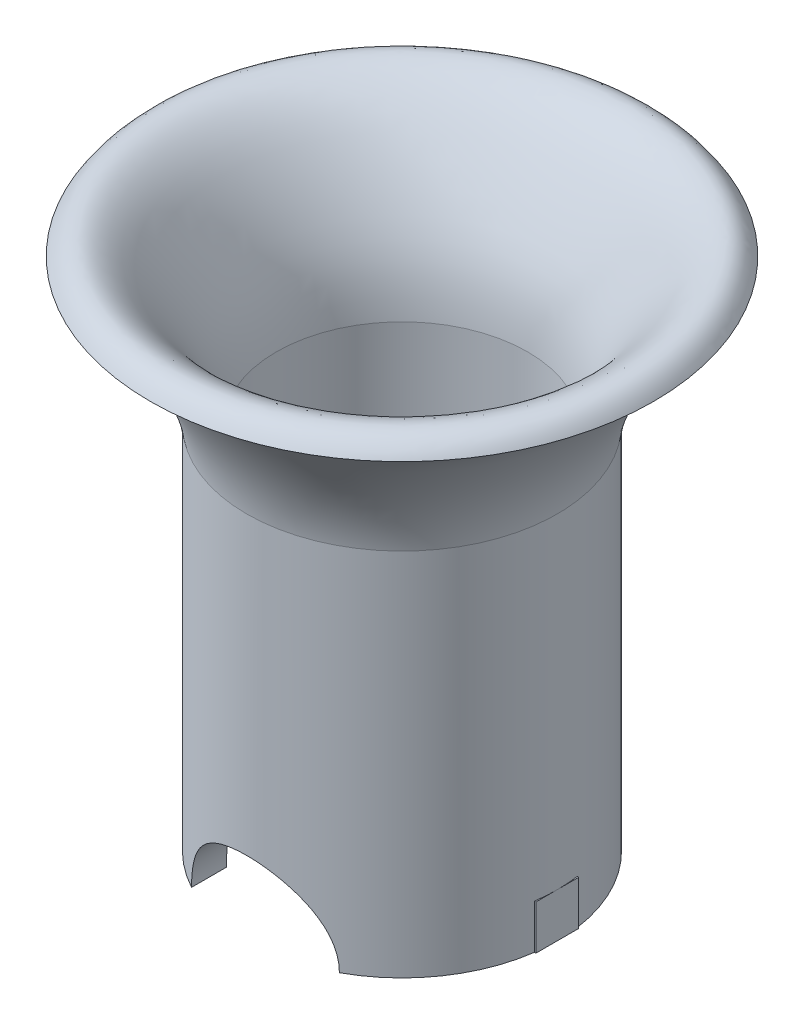
SolidWorks part; units mm, degrees
ref_plane "Front Plane" through (0, 0, 0) normal (0, 0, 1) x (1, 0, 0)
ref_plane "Top Plane" through (0, 0, 0) normal (0, 1, 0) x (1, 0, 0)
ref_plane "Right Plane" through (0, 0, 0) normal (1, 0, 0) x (0, 0, -1)
sketch "Sketch1" plane through (0, 0, 0) normal (0, 0, 1) x (1, 0, 0)
  line L0 (0, 0) -> (-8.5, 0) construction
  line L1 (-8.5, 0) -> (-8.5, 25)
  line L2 (-8.5, 0) -> (-10.5, 0)
  line L3 (-10.5, 0) -> (-10.5, 25)
  line L5 (0, 0) -> (0, 26.9305) construction
  spline S0 degree 3 poles (-8.5, 25) (-8.597, 26.015) (-8.907, 27.9673) (-10.2035, 30.7165) (-11.7469, 33.1056) (-13.7772, 35.5008) (-16.0448, 36.4741) (-17.0155, 34.8472) knots 0 0 0 0 0.199433 0.381103 0.589074 0.751073 1 1 1 1
  spline S1 degree 3 poles (-17.0155, 34.8472) (-15.0617, 34.1491) (-12.5469, 30.7995) (-10.7724, 27.1394) (-10.5, 25) knots 0 0 0 0 0.483303 1 1 1 1
  point P7 (-11.9319, 26.5136)
  point P8 (-12.9781, 28.0108)
  point P16 (-15.1906, 33.2508)
  point P18 (-12.6295, 30.1998)
  point P20 (-11.3225, 28.0108)
  point P22 (-17.0155, 34.8472)
  point P23 (-14.837, 33.482)
  point P24 (-12.8038, 30.8388)
  dimension "D1" = 8.5
  dimension "D2" = 25
  dimension "D3" = 25
revolve "Revolve1" add sketch "Sketch1" angle 360 about L5
sketch "Sketch3" plane through (0, 0, 0) normal (0, 0, 1) x (1, 0, 0)
  line L0 (-10.5, 0) -> (10.5, 0) construction
  line L1 (-2.5, 0) -> (10.5, 0)
  line L2 (-2.5, 0) -> (-2.5, 3)
  line L3 (-2.5, 3) -> (10.5, 3)
  line L4 (10.5, 0) -> (10.5, 3)
  line L5 (10.5, 0) -> (10.5, 25) construction
  line L6 (-2.5, 1.5) -> (0, 1.5) construction
  line L7 (0, 1.5) -> (0, 0) construction
  circle A0 centre (0, 1.5) radius 0.5
  dimension "D3" = 1
  dimension "D1" = 3
  dimension "D2" = 13
extrude "Boss-Extrude1" add sketch "Sketch3" along normal blind 1.45 and the other way blind 1.45
sketch "Sketch4" plane through (0, 0, 1.45) normal (0, 0, 1) x (1, 0, 0)
  circle A0 centre (0, 0) radius 5
extrude "Cut-Extrude1" cut sketch "Sketch4" along normal blind 20
fillet "Fillet1" radius 2 2 edges at (2.9377, 3, -1.45) (2.9377, 3, 1.45)
